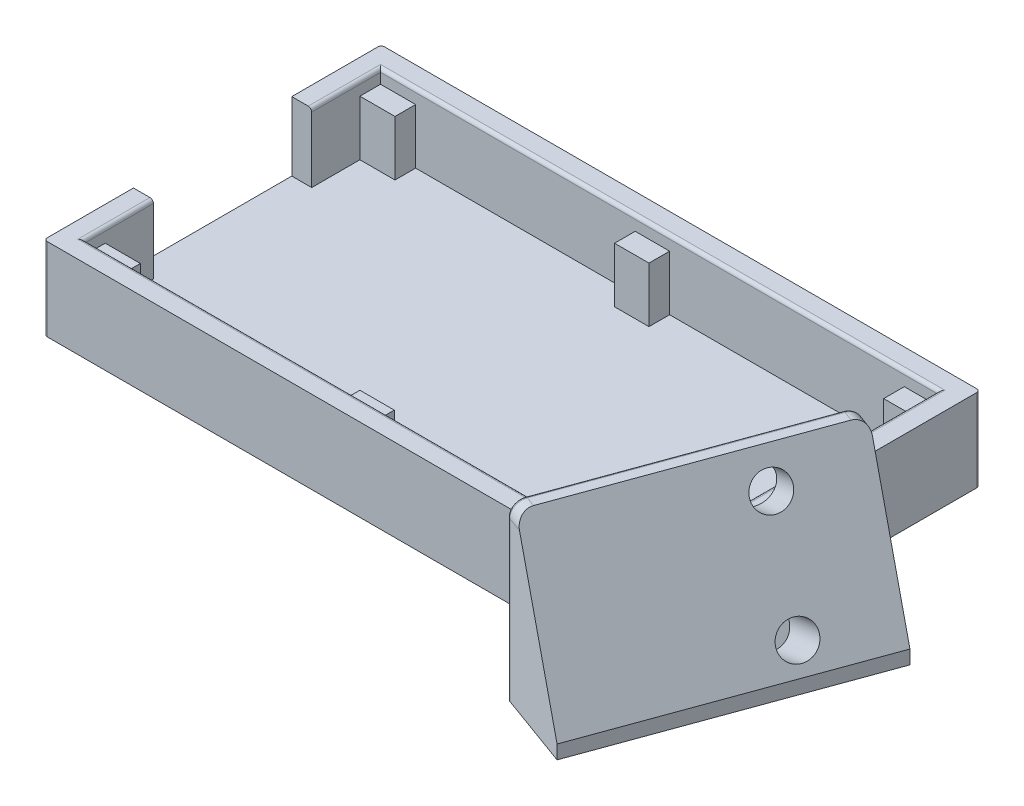
SolidWorks part; units mm, degrees
note: The reader was unsure of these and kept them because the rebuilt part matched: shared geometry of "Sketch1<4>".
ref_plane "Front Plane" through (0, 0, 0) normal (0, 0, 1) x (1, 0, 0)
ref_plane "Top Plane" through (0, 0, 0) normal (0, 1, 0) x (1, 0, 0)
ref_plane "Right Plane" through (0, 0, 0) normal (1, 0, 0) x (0, 0, -1)
sketch "Sketch1" plane through (0, 0, 0) normal (0, 1, 0) x (1, 0, 0)
  line L0 (8, 46) -> (39.9, 46)
  line L1 (0, 0) -> (87, 0)
  line L2 (0, 0) -> (0, 49)
  line L3 (0, 49) -> (87, 49)
  line L4 (87, 0) -> (87, 49)
  line L5 (8, 3) -> (39.9, 3)
  line L6 (0, 36) -> (2.9, 36)
  line L7 (2.9, 36) -> (2.9, 43)
  line L8 (2.9, 6) -> (2.9, 13)
  line L9 (2.9, 13) -> (0, 13)
  line L10 (83.9, 43) -> (83.9, 6)
  line L12 (73, 0) -> (84, -12)
  line L13 (84, -12) -> (87, 0)
  line L14 (39.9, 46) -> (39.9, 43)
  line L15 (39.9, 43) -> (44.9, 43)
  line L16 (44.9, 43) -> (44.9, 46)
  line L17 (44.9, 46) -> (79, 46)
  line L18 (39.9, 3) -> (39.9, 6)
  line L19 (39.9, 6) -> (44.9, 6)
  line L20 (44.9, 6) -> (44.9, 3)
  line L21 (44.9, 3) -> (79, 3)
  line L22 (79, 3) -> (79, 6)
  line L23 (79, 6) -> (83.9, 6)
  line L24 (79, 46) -> (79, 43)
  line L25 (79, 43) -> (83.9, 43)
  line L26 (8, 46) -> (8, 43)
  line L27 (8, 43) -> (2.9, 43)
  line L28 (8, 3) -> (8, 6)
  line L29 (8, 6) -> (2.9, 6)
  point P43 (87, 0)
sketch "Sketch2" plane through (0, 0, 0) normal (0, 0, 1) x (1, 0, 0)
  line L0 (90, 0) -> (102, 0)
  line L1 (102, 0) -> (102, 2)
  line L2 (102, 2) -> (92, 25)
  line L3 (92, 25) -> (90, 25)
  line L4 (90, 25) -> (90, 0)
extrude "Boss-Extrude1" add sketch "Sketch2" along normal blind 40
move or copy body "Body-Move/Copy1" bodies to move or copy 101 copy no rotation origin (95, 0, 20) rotation axis (0, -1, 0) rotation angle 20
move or copy body "Body-Move/Copy2" bodies to move or copy 102 copy no translate (-4, 0, -25) parameters "D1"=4, "D2"=0, "D3"=25
extrude "Boss-Extrude2" add sketch "Sketch1" along normal blind 2
extrude "Boss-Extrude3" add sketch "Sketch1<4>" along normal blind 12 contours L0 L10 L5 L8 L9 L2 L1 L4 L3 L6 L7
sketch "Sketch1<4>" plane through (0, 0, 0) normal (0, 1, 0) x (1, 0, 0) same geometry as "Sketch1"
sketch "Sketch4" plane through (72.4478, 33.5206, 26.3688) normal (0.8618, 0.3987, 0.3137) x (0.3002, 0.0976, -0.9489)
  line L0 (12.0749, -35.8595) -> (39.9159, -38.8391) construction
  line L1 (12.0749, -35.8595) -> (51.8478, -40.1161) construction
  line L2 (48.1735, -39.7229) -> (50.5995, -17.0548) construction
  line L3 (39.9159, -38.8391) -> (40.3416, -34.8618) construction
  line L4 (40.3416, -34.8618) -> (42.0442, -18.9527) construction
  circle A3 centre (42.0442, -18.9527) radius 2.5
  circle A4 centre (40.3416, -34.8618) radius 2.5
extrude "Cut-Extrude2" cut sketch "Sketch4" against normal blind 8
fillet "Fillet1" radius 2 2 edges at (94.0816, 25, -25.1619) (80.4008, 25, 12.4258)
sketch "Sketch10" plane through (0, 12, 0) normal (0, 1, 0) x (1, 0, 0)
  line L5 (83.9, 6) -> (79, 6)
  line L11 (39.9, 3) -> (45, 3)
  line L12 (39.9, 3) -> (39.9, 6)
  line L13 (39.9, 6) -> (45, 6)
  line L14 (45, 3) -> (45, 6)
  line L15 (39.9, 46) -> (44.9, 46)
  line L16 (39.9, 46) -> (39.9, 43)
  line L17 (39.9, 43) -> (44.9, 43)
  line L18 (44.9, 46) -> (44.9, 43)
  line L32 (83.9, 6) -> (83.9, 3)
  line L33 (83.9, 3) -> (79, 3)
  line L39 (79, 6) -> (79, 3)
  line L40 (83.9, 43) -> (79, 43)
  line L41 (83.9, 43) -> (83.9, 46)
  line L42 (83.9, 46) -> (79, 46)
  line L43 (79, 43) -> (79, 46)
  line L44 (8, 46) -> (2.9, 46)
  line L45 (8, 46) -> (8, 43)
  line L46 (8, 43) -> (2.9, 43)
  line L47 (2.9, 46) -> (2.9, 43)
  line L48 (8, 3) -> (2.9, 3)
  line L49 (8, 3) -> (8, 6)
  line L50 (8, 6) -> (2.9, 6)
  line L51 (2.9, 3) -> (2.9, 6)
extrude "Cut-Extrude4" cut sketch "Sketch10" against normal blind 2
fillet "Fillet2" radius 0.5 13 edges at (2.9, 12, -8) (2.9, 12, -41) (0, 6, 0) (87, 6, -49) (0, 6, -49) (92.9416, 24.4142, -24.9535) (86.3015, 25, -6.7101) (79.6615, 24.4142, 11.5333) (93.1419, 11.5, -25.504) (79.4611, 11.5, 12.0838) (43.4, 12, -3) (83.9, 12, -24.5) (43.4, 12, -46)
